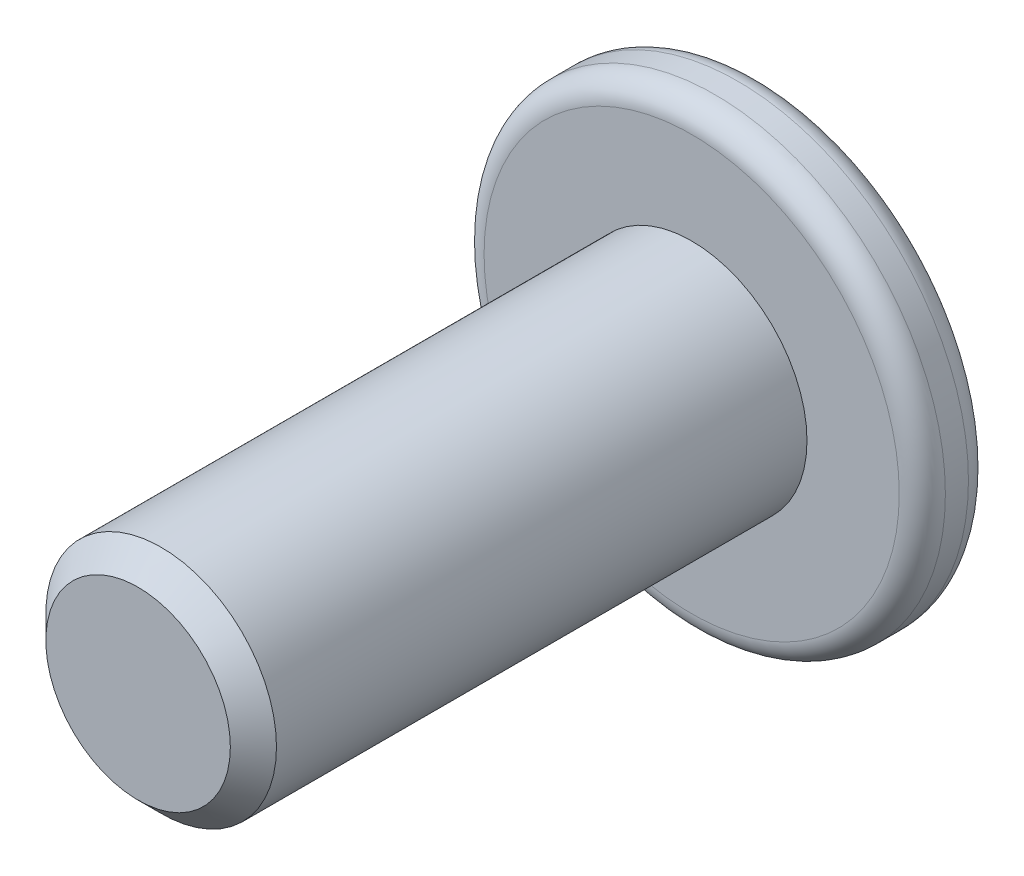
SolidWorks part; units mm, degrees
material "Alloy Steel"
ref_plane "Front Plane" through (0, 0, 0) normal (0, 0, 1) x (1, 0, 0)
ref_plane "Top Plane" through (0, 0, 0) normal (0, 1, 0) x (1, 0, 0)
ref_plane "Right Plane" through (0, 0, 0) normal (1, 0, 0) x (0, 0, -1)
sketch "Sketch1" plane through (0, 0, 0) normal (0, 0, 1) x (1, 0, 0)
  circle A0 centre (0, 0) radius 10
  circle A1 centre (0, 0) radius 5
  dimension "D1" = 20
  dimension "D2" = 10
extrude "Boss-Extrude1" add sketch "Sketch1" along normal blind 3 contours A1 | A0 A1 | A1 | A0 region at (-9.7172, 0, 0) region at (0, 0, 0)
extrude "Boss-Extrude2" add sketch "Sketch1<3>" along normal blind 27 contours A1 region at (0, 0, 0)
sketch "Sketch1<3>" plane through (0, 0, 0) normal (0, 0, 1) x (1, 0, 0) same geometry as "Sketch1"
chamfer "Chamfer1" distance 1 angle 45 1 edges at (5, 0, 27)
fillet "Fillet1" radius 1 2 edges at (10, 0, 3) (10, 0, 0)
